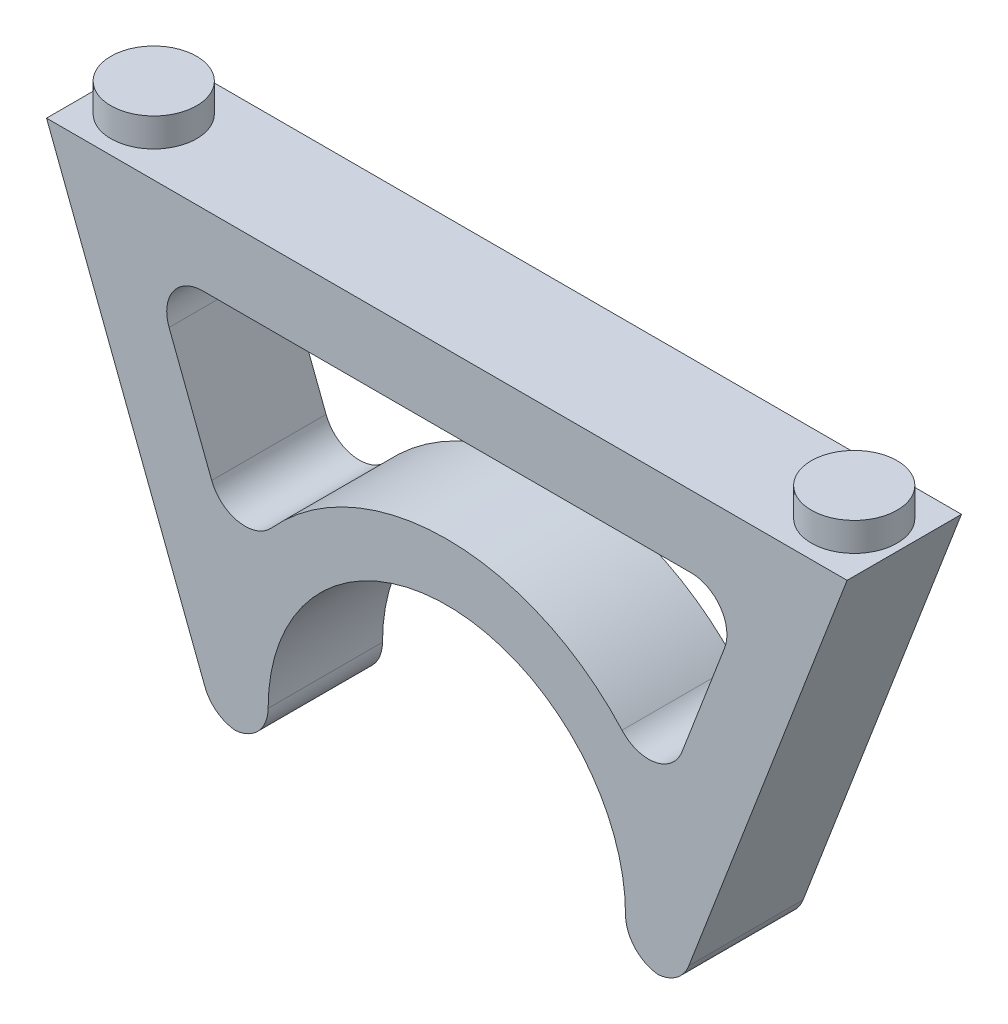
SolidWorks part; units mm, degrees
ref_plane "Front Plane" through (0, 0, 0) normal (0, 0, 1) x (1, 0, 0)
ref_plane "Top Plane" through (0, 0, 0) normal (0, 1, 0) x (1, 0, 0)
ref_plane "Right Plane" through (0, 0, 0) normal (1, 0, 0) x (0, 0, -1)
sketch "Sketch1" plane through (0, 0, 0) normal (0, 0, 1) x (1, 0, 0)
  line L0 (-28, 0) -> (28, 0)
  line L1 (-12.2474, -30.5) -> (-16.3095, -30.5)
  line L2 (12.2474, -30.5) -> (16.3095, -30.5)
  line L3 (-28, 0) -> (-16.3095, -30.5)
  line L5 (28, 0) -> (16.3095, -30.5)
  arc A0 (-12.2474, -30.5) -> (12.2474, -30.5) centre (0, -28) cw
  point P7 (0, 0)
  point P8 (0, 0)
  dimension "D3" = 12.5
  dimension "D6" = 4.0621
  dimension "D1" = 56
  dimension "D2" = 28
  dimension "D4" = 2.5
  dimension "D5" = 4.0621
  dimension "D7" = 2.5
extrude "Boss-Extrude1" add sketch "Sketch1" along normal blind 8
sketch "Sketch2" plane through (0, 0, 8) normal (0, 0, 1) x (1, 0, 0)
  line L0 (-20.7288, -5) -> (-14.7486, -20.6021)
  line L1 (-28, 0) -> (-16.3095, -30.5) construction
  line L3 (28, 0) -> (-28, 0) construction
  line L4 (0, -4.4) -> (0, 4.4) construction
  line L5 (20.7288, -5) -> (14.7486, -20.6021)
  line L6 (-20.7288, -5) -> (20.7288, -5)
  arc A0 (-14.7486, -20.6021) -> (14.7486, -20.6021) centre (0, -28) cw
  dimension "D3" = 16.5
  dimension "D1" = 5
  dimension "D2" = 28
  dimension "D4" = 5
extrude "Cut-Extrude1" cut sketch "Sketch2" against normal through all
fillet "Fillet1" radius 2.5 8 edges at (12.2474, -30.5, 4) (16.3095, -30.5, 4) (-12.2474, -30.5, 4) (-16.3095, -30.5, 4) (14.7486, -20.6021, 4) (20.7288, -5, 4) (-20.7288, -5, 4) (-14.7486, -20.6021, 4)
sketch "Sketch3" plane through (0, 0, 0) normal (0, 1, 0) x (1, 0, 0)
  line L1 (28, -8) -> (-28, -8) construction
  line L3 (-28, -8) -> (-28, 0) construction
  circle A0 centre (-24.5, -4) radius 3
  circle A1 centre (24.5, -4) radius 3
  dimension "D2" = 6
  dimension "D1" = 4
  dimension "D3" = 49
  dimension "D4" = 3.5
extrude "Boss-Extrude2" add sketch "Sketch3" along normal blind 2
